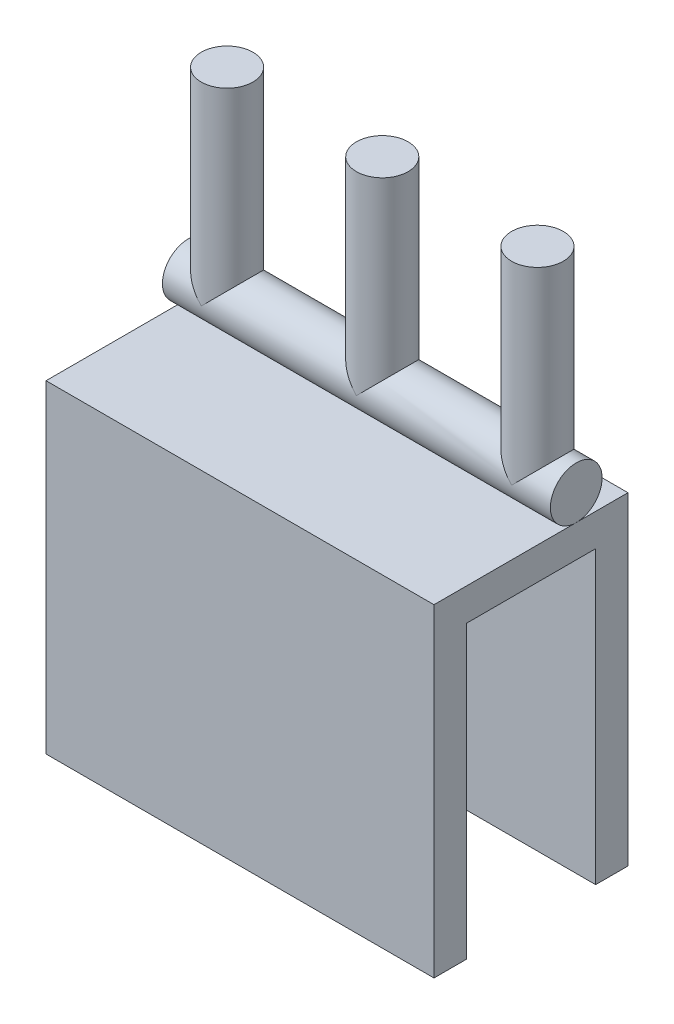
SolidWorks part; units mm, degrees
ref_plane "정면" through (0, 0, 0) normal (0, 0, 1) x (1, 0, 0)
ref_plane "윗면" through (0, 0, 0) normal (0, 1, 0) x (1, 0, 0)
ref_plane "우측면" through (0, 0, 0) normal (1, 0, 0) x (0, 0, -1)
sketch "스케치1" plane through (0, 0, 0) normal (1, 0, 0) x (0, 0, -1)
  line L0 (-50, -125) -> (-75, -125)
  line L1 (75, -125) -> (50, -125)
  line L2 (75, -125) -> (75, 125)
  line L3 (75, 125) -> (-75, 125)
  line L4 (-75, -125) -> (-75, 125)
  line L5 (75, -125) -> (-75, 125) construction
  line L6 (75, 125) -> (-75, -125) construction
  line L8 (-50, -125) -> (-50, 100)
  line L9 (-50, 100) -> (50, 100)
  line L10 (50, -125) -> (50, 100)
  point P0 (0, 0)
  dimension "D1" = 100
  dimension "D2" = 25
  dimension "D3" = 150
  dimension "D4" = 250
  dimension "D5" = 225
extrude "보스-돌출1" add sketch "스케치1" along normal blind 300
sketch "스케치2" plane through (0, 0, 0) normal (1, 0, 0) x (0, 0, -1)
  line L0 (75, 125) -> (-75, 125) construction
  line L1 (75, -125) -> (75, 125) construction
  circle A0 centre (35, 145) radius 20
  dimension "D1" = 20
  dimension "D2" = 40
extrude "보스-돌출2" add sketch "스케치2" along normal blind 300 separate body
ref_plane "평면1" through (0, 145, 0) normal (0, 1, 0) x (1, 0, 0)
sketch "스케치3" plane through (0, 145, 0) normal (0, 1, 0) x (1, 0, 0)
  line L0 (0, 35) -> (300, 35) construction
  line L1 (0, 55) -> (0, 15) construction
  line L2 (300, 15) -> (300, 55) construction
  circle A0 centre (30, 35) radius 20
  circle A1 centre (150, 35) radius 20
  circle A2 centre (270, 35) radius 20
  dimension "D1" = 30
  dimension "D2" = 30
extrude "보스-돌출3" add sketch "스케치3" along normal blind 150
